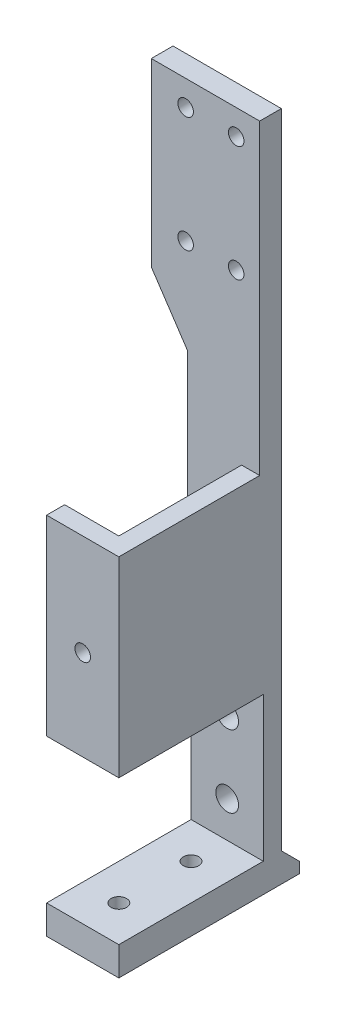
SolidWorks part; units mm, degrees
ref_plane "前视基准面" through (0, 0, 0) normal (0, 0, 1) x (1, 0, 0)
ref_plane "上视基准面" through (0, 0, 0) normal (0, 1, 0) x (1, 0, 0)
ref_plane "右视基准面" through (0, 0, 0) normal (1, 0, 0) x (0, 0, -1)
sketch "草图1" plane through (0, 0, 0) normal (0, 1, 0) x (1, 0, 0)
  line L1 (0, 0) -> (35, 0)
  line L2 (0, 0) -> (0, 80)
  line L3 (0, 80) -> (35, 80)
  line L4 (35, 0) -> (35, 80)
  circle A0 centre (25, 30) radius 2.15
  circle A1 centre (25, 10) radius 2.15
  dimension "D6" = 4.3
  dimension "D1" = 35
  dimension "D2" = 80
  dimension "D3" = 10
  dimension "D4" = 10
  dimension "D5" = 20
extrude "凸台-拉伸1" add sketch "草图1" along normal blind 30
sketch "草图3" plane through (0, 30, 0) normal (0, 1, 0) x (1, 0, 0)
  line L0 (35, 0) -> (35, 80) construction
  line L1 (35, 40) -> (0, 40)
  line L2 (35, 40) -> (35, 45)
  line L3 (35, 45) -> (0, 45)
  line L4 (0, 40) -> (0, 45)
  line L5 (0, 80) -> (0, 0) construction
  line L6 (0, 0) -> (35, 0) construction
  dimension "D1" = 5
  dimension "D2" = 40
extrude "凸台-拉伸2" add sketch "草图3" along normal blind 40
sketch "草图4" plane through (0, 0, 0) normal (-1, 0, 0) x (0, 0, 1)
  line L0 (-40, 70) -> (-40, 30) construction
  line L1 (0, 0) -> (-40, 0)
  line L2 (0, 0) -> (0, 22)
  line L3 (0, 22) -> (-40, 22)
  line L4 (-40, 0) -> (-40, 22)
  line L5 (-80, 30) -> (-50, 30)
  line L6 (-80, 30) -> (-80, 10)
  line L7 (-80, 10) -> (-50, 10)
  line L8 (-50, 30) -> (-50, 10)
  line L10 (-40, 30) -> (0, 30) construction
  line L11 (-45, 70) -> (-45, 30) construction
  dimension "D1" = 8
  dimension "D2" = 20
  dimension "D3" = 5
extrude "切除-拉伸2" cut sketch "草图4" against normal blind 70
chamfer "倒角1" distance 5 angle 45 1 edges at (17.5, 30, -50)
sketch "草图7" plane through (0, 0, -45) normal (0, 0, -1) x (-1, 0, 0)
  line L0 (-35, 70) -> (-35, 30) construction
  line L1 (-35, 70) -> (0, 70) construction
  circle A0 centre (-25, 60) radius 3.15
  circle A1 centre (-25, 40) radius 3.15
  dimension "D2" = 6.3
  dimension "D1" = 10
  dimension "D3" = 10
  dimension "D4" = 20
extrude "切除-拉伸3" cut sketch "草图7" against normal blind 70
sketch "草图8" plane through (0, 30, 0) normal (0, 1, 0) x (1, 0, 0)
  line L0 (0, 0) -> (15, 0)
  line L1 (0, 0) -> (35, 0) construction
  line L2 (15, 0) -> (0, 36)
  line L3 (0, 40) -> (0, 0) construction
  line L4 (0, 36) -> (0, 0)
  dimension "D1" = 20
  dimension "D2" = 4
extrude "切除-拉伸4" cut sketch "草图8" against normal blind 70
sketch "草图9" plane through (0, 70, 0) normal (0, 1, 0) x (1, 0, 0)
  line L0 (35, 45) -> (0, 45) construction
  line L1 (35, 45) -> (0, 45)
  line L5 (0, 40) -> (0, 36)
  line L6 (0, 36) -> (15, 0)
  line L7 (15, 0) -> (35, 0)
  line L8 (35, 0) -> (35, 40)
  line L9 (35, 40) -> (0, 40)
  line L10 (0, 45) -> (0, 36)
  line L11 (0, 36) -> (15, 0)
  line L12 (15, 0) -> (35, 0)
  line L13 (35, 0) -> (35, 45)
  circle A0 centre (25, 30) radius 2.15 construction
  circle A1 centre (25, 30) radius 2.15
  circle A2 centre (25, 10) radius 2.15 construction
  circle A3 centre (25, 10) radius 2.15
  dimension "D1" = 0
extrude "凸台-拉伸3" add sketch "草图9" along normal blind 8
sketch "草图10" plane through (0, 0, 0) normal (-1, 0, 0) x (0, 0, 1)
  line L0 (-45, 78) -> (-40, 78) construction
  line L45 (-45, 78) -> (-45, 30) construction
  line L46 (-40, 70) -> (-40, 30) construction
  line L47 (0, 30) -> (-36, 30) construction
  line L48 (-80, 156) -> (-40, 156)
  line L49 (-80, 146) -> (-80, 156)
  line L50 (-50, 146) -> (-80, 146)
  line L51 (-40, 22) -> (-36, 22)
  line L52 (-36, 22) -> (-36, 30)
  line L53 (-36, 30) -> (-40, 30)
  line L54 (-40, 30) -> (-40, 70)
  line L55 (-40, 70) -> (-36, 70)
  line L56 (-36, 70) -> (-36, 78)
  line L57 (-36, 78) -> (-45, 78)
  line L58 (-45, 78) -> (-45, 30)
  line L59 (-45, 30) -> (-50, 25)
  line L60 (-50, 25) -> (-50, 10)
  line L61 (-50, 10) -> (-80, 10)
  line L62 (-80, 10) -> (-80, 0)
  line L63 (-80, 0) -> (-40, 0)
  line L64 (-40, 0) -> (-40, 22)
  line L65 (-40, 22) -> (-36, 22)
  line L66 (-36, 22) -> (-36, 30)
  line L67 (-36, 30) -> (-40, 30)
  line L68 (-40, 30) -> (-40, 78)
  line L72 (-45, 126) -> (-45, 78)
  line L73 (-45, 30) -> (-50, 25)
  line L74 (-50, 25) -> (-50, 10)
  line L75 (-50, 10) -> (-80, 10)
  line L76 (-80, 10) -> (-80, 0)
  line L77 (-80, 0) -> (-40, 0)
  line L78 (-40, 0) -> (-40, 22)
  line L79 (-50, 131) -> (-50, 146)
  line L80 (-45, 126) -> (-50, 131)
  line L81 (-40, 156) -> (-40.5, 78)
  line L82 (-45, 78) -> (-36, 78) construction
  line L83 (-40.5, 78) -> (-45, 78)
  line L84 (-45, 78) -> (-45, 30)
  dimension "D2" = 48
  dimension "D1" = 0
extrude "凸台-拉伸4" add sketch "草图10" against normal through all
sketch "草图2" plane through (0, 30, 0) normal (0, 1, 0) x (1, 0, 0)
  line L0 (0, 40) -> (0, 36) construction
  line L1 (35, 80) -> (0, 80) construction
  circle A0 centre (10, 70) radius 4.1
  dimension "D3" = 8.2
  dimension "D1" = 10
  dimension "D2" = 10
extrude "切除-拉伸5" cut sketch "草图2" against normal through all and the other way through all
sketch "草图11" plane through (0, 0, 0) normal (0, 0, 1) x (1, 0, 0)
  line L0 (35, 0) -> (0, 0) construction
  line L1 (0, 156) -> (15, 156)
  line L2 (0, 156) -> (0, 0)
  line L3 (0, 0) -> (15, 0)
  line L4 (15, 156) -> (15, 0)
  line L5 (35, 22) -> (35, 0) construction
  dimension "D1" = 20
extrude "切除-拉伸6" cut sketch "草图11" against normal through all and the other way through all
sketch "草图13" plane through (35, 0, 0) normal (1, 0, 0) x (0, 0, -1)
  line L1 (40, 22) -> (80, 22)
  line L2 (40, 22) -> (40, 0)
  line L3 (40, 0) -> (80, 0)
  line L4 (80, 22) -> (80, 0)
extrude "切除-拉伸7" cut sketch "草图13" against normal through all
sketch "草图19" plane through (15, 0, 0) normal (-1, 0, 0) x (0, 0, 1)
  line L0 (0, 78) -> (-40.5, 78) construction
  line L1 (-80, 156) -> (-34.0016, 156)
  line L2 (-80, 156) -> (-80, 78)
  line L3 (-80, 78) -> (-34.0016, 78)
  line L4 (-34.0016, 156) -> (-34.0016, 78)
extrude "切除-拉伸11" cut sketch "草图19" against normal blind 56
sketch "草图21" plane through (0, 0, -45) normal (0, 0, -1) x (-1, 0, 0)
  line L0 (-35, 78) -> (-35, 208)
  line L1 (-35, 208) -> (-5, 208)
  line L2 (-5, 208) -> (-5, 158)
  line L3 (-5, 158) -> (-15, 143)
  line L4 (-15, 143) -> (-15, 78)
  line L5 (-35, 78) -> (-15, 78)
  circle A0 centre (-28.5, 201) radius 2.15
  circle A1 centre (-14.5, 201) radius 2.15
  circle A2 centre (-28.5, 169) radius 2.15
  circle A3 centre (-14.5, 169) radius 2.15
  dimension "D9" = 4.3
  dimension "D1" = 30
  dimension "D2" = 50
  dimension "D3" = 15
  dimension "D4" = 130
  dimension "D5" = 6.5
  dimension "D6" = 14
  dimension "D7" = 7
  dimension "D8" = 32
extrude "凸台-拉伸8" add sketch "草图21" against normal blind 6
sketch "草图22" plane through (35, 0, 0) normal (1, 0, 0) x (0, 0, -1)
  line L0 (0, 78) -> (39, 78)
  line L1 (39, 78) -> (39, 123)
  line L2 (39, 208) -> (39, 78) construction
  line L5 (0, 123) -> (0, 78)
  line L6 (39, 123) -> (0, 123)
  dimension "D1" = 45
  dimension "D2" = 45
extrude "凸台-拉伸9" add sketch "草图22" against normal blind 5
sketch "草图23" plane through (0, 0, 0) normal (0, 0, 1) x (1, 0, 0)
  line L1 (35, 70) -> (15, 70)
  line L2 (35, 70) -> (35, 123)
  line L3 (35, 123) -> (15, 123)
  line L4 (15, 70) -> (15, 123)
  circle A0 centre (25, 95) radius 2.15
  dimension "D5" = 4.3
  dimension "D1" = 20
  dimension "D2" = 10
  dimension "D3" = 25
extrude "凸台-拉伸10" add sketch "草图23" against normal blind 5
